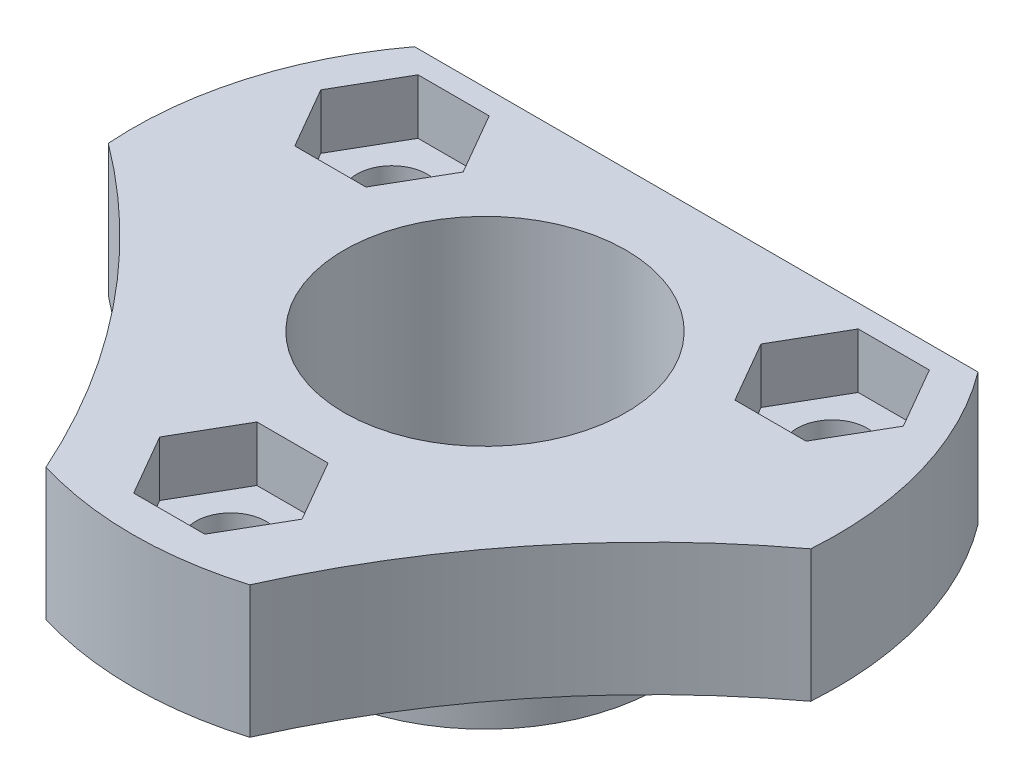
SolidWorks part; units mm, degrees
material "ABS"
ref_plane "Plan de face" through (0, 0, 0) normal (0, 0, 1) x (1, 0, 0)
ref_plane "Plan de dessus" through (0, 0, 0) normal (0, 1, 0) x (1, 0, 0)
ref_plane "Plan de droite" through (0, 0, 0) normal (1, 0, 0) x (0, 0, -1)
sketch "Esquisse1" plane through (0, 0, 0) normal (0, 1, 0) x (1, 0, 0)
  circle A0 centre (0, 0) radius 6.4
  circle A1 centre (0, 0) radius 16
  circle A7 centre (0, -11.547) radius 1.6
  circle A8 centre (-10, 5.7735) radius 1.6
  circle A9 centre (10, 5.7735) radius 1.6
  point P22 (0, 0)
  dimension "D1" = 12.8
  dimension "D2" = 32
  dimension "D3" = 3
  dimension "D5" = 20
  dimension "D6" = 3.2
extrude "Boss.-Extru.1" add sketch "Esquisse1" along normal blind 6
sketch "Esquisse2" plane through (0, 0, 0) normal (0, -1, 0) x (1, 0, 0)
  circle A0 centre (0, 0) radius 8
  circle A1 centre (0, 0) radius 6.4
  circle A3 centre (0, 0) radius 6.4 construction
  dimension "D1" = 16
extrude "Boss.-Extru.2" add sketch "Esquisse2" along normal blind 4
chamfer "Chanfrein1" distance 0.5 angle 45 2 edges at (0, -4, -6.4) (0, 0, 8)
sketch "Esquisse3" plane through (0, 6, 0) normal (0, 1, 0) x (1, 0, 0)
  line L0 (-37.5, -30) -> (37.5, -30) construction
  line L1 (-32.5116, 29.8667) -> (31.4819, 29.8667)
  line L2 (-32.5116, 29.8667) -> (-32.5116, 9.6)
  line L3 (-32.5116, 9.6) -> (31.4819, 9.6)
  line L4 (31.4819, 29.8667) -> (31.4819, 9.6)
  line L5 (0, 0) -> (0, -30) construction
  circle A0 centre (-37.5, -30) radius 36
  circle A1 centre (37.5, -30) radius 36
  dimension "D1" = 72
  dimension "D2" = 75
  dimension "D3" = 30
  dimension "D4" = 9.6
extrude "Enlèv. mat.-Extru.1" cut sketch "Esquisse3" against normal through all
sketch "Esquisse4" plane through (0, 6, 0) normal (0, 1, 0) x (1, 0, 0)
  line L1 (-8.3834, 2.9735) -> (-6.7668, 5.7735)
  line L2 (-6.7668, 5.7735) -> (-8.3834, 8.5735)
  line L3 (-8.3834, 8.5735) -> (-11.6166, 8.5735)
  line L4 (-11.6166, 8.5735) -> (-13.2332, 5.7735)
  line L5 (-13.2332, 5.7735) -> (-11.6166, 2.9735)
  line L6 (-11.6166, 2.9735) -> (-8.3834, 2.9735)
  line L7 (11.6166, 2.9735) -> (13.2332, 5.7735)
  line L8 (13.2332, 5.7735) -> (11.6166, 8.5735)
  line L9 (11.6166, 8.5735) -> (8.3834, 8.5735)
  line L10 (8.3834, 8.5735) -> (6.7668, 5.7735)
  line L11 (6.7668, 5.7735) -> (8.3834, 2.9735)
  line L12 (8.3834, 2.9735) -> (11.6166, 2.9735)
  line L13 (1.6166, -14.347) -> (3.2332, -11.547)
  line L14 (3.2332, -11.547) -> (1.6166, -8.747)
  line L15 (1.6166, -8.747) -> (-1.6166, -8.747)
  line L16 (-1.6166, -8.747) -> (-3.2332, -11.547)
  line L17 (-3.2332, -11.547) -> (-1.6166, -14.347)
  line L18 (-1.6166, -14.347) -> (1.6166, -14.347)
  circle A0 centre (-10, 5.7735) radius 2.8 construction
  circle A1 centre (10, 5.7735) radius 2.8 construction
  circle A2 centre (0, -11.547) radius 2.8 construction
  dimension "D1" = 5.6
extrude "Enlèv. mat.-Extru.2" cut sketch "Esquisse4" against normal blind 2.5
